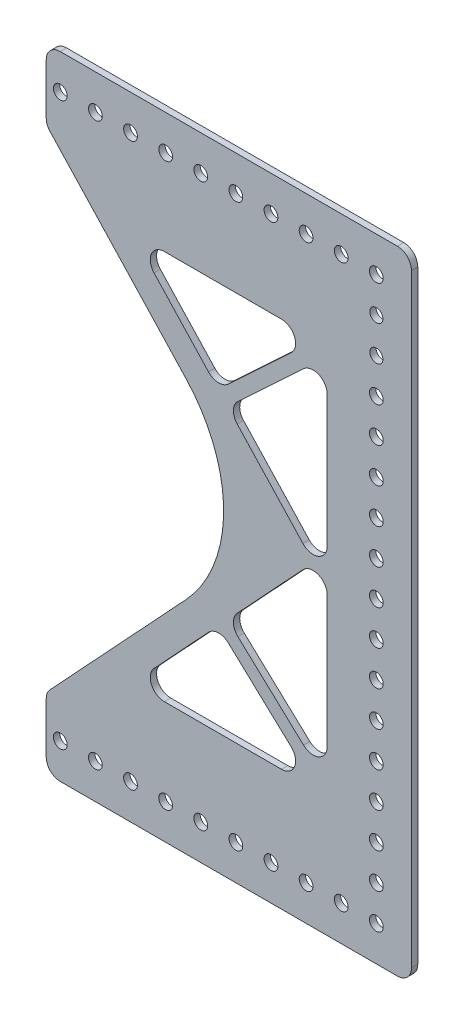
SolidWorks part; units mm, degrees
ref_plane "Front Plane" through (0, 0, 0) normal (0, 0, 1) x (1, 0, 0)
ref_plane "Top Plane" through (0, 0, 0) normal (0, 1, 0) x (1, 0, 0)
ref_plane "Right Plane" through (0, 0, 0) normal (1, 0, 0) x (0, 0, -1)
sketch "Sketch1" plane through (0, 0, 0) normal (0, 0, 1) x (1, 0, 0)
  line L0 (238.8067, 781.2872) -> (222.2967, 781.2872)
  line L4 (176.5767, 781.2872) -> (116.8867, 781.2872)
  line L5 (113.1687, 754.4243) -> (162.3479, 701.6037)
  line L6 (243.8867, 776.2072) -> (243.8867, 666.9872)
  line L7 (111.8067, 757.8859) -> (111.8067, 776.2072)
  line L8 (150.787, 728.9305) -> (170.4738, 707.786)
  line L9 (213.4067, 674.5852) -> (213.4067, 722.2064)
  line L10 (196.902, 737.4722) -> (154.5049, 737.4722)
  line L11 (243.8867, 557.7672) -> (243.8867, 666.9872)
  line L12 (238.8067, 552.6872) -> (222.2967, 552.6872)
  line L16 (113.1687, 579.55) -> (162.3479, 632.3706)
  line L17 (176.5767, 552.6872) -> (116.8867, 552.6872)
  line L18 (111.8067, 576.0884) -> (111.8067, 557.7672)
  line L19 (200.3636, 728.6742) -> (177.6534, 707.5296)
  line L20 (180.8588, 637.3423) -> (204.6087, 662.8508)
  line L21 (204.8651, 725.9243) -> (181.1151, 703.8117)
  line L22 (180.8588, 696.632) -> (204.6087, 671.1235)
  line L23 (213.4067, 659.3892) -> (213.4067, 611.768)
  line L24 (204.8651, 608.05) -> (181.1151, 630.1627)
  line L25 (200.3636, 605.3001) -> (177.6534, 626.4447)
  line L26 (150.787, 605.0438) -> (170.4738, 626.1884)
  line L27 (196.902, 596.5022) -> (154.5049, 596.5022)
  line L28 (222.2967, 552.6872) -> (176.5767, 552.6872)
  line L29 (222.2967, 781.2872) -> (176.5767, 781.2872)
  arc A0 (238.8067, 781.2872) -> (243.8867, 776.2072) centre (238.8067, 776.2072) cw
  arc A5 (116.8867, 781.2872) -> (111.8067, 776.2072) centre (116.8867, 776.2072) ccw
  circle A6 centre (142.2867, 768.5872) radius 2.4892
  circle A7 centre (154.9867, 768.5872) radius 2.4892
  circle A8 centre (167.6867, 768.5872) radius 2.4892
  circle A9 centre (231.1867, 743.1872) radius 2.3719
  circle A10 centre (231.1867, 730.4872) radius 2.4892
  circle A11 centre (231.1867, 717.7872) radius 2.4892
  circle A12 centre (231.1867, 705.0872) radius 2.4892
  circle A13 centre (231.1867, 692.3872) radius 2.4892
  arc A14 (113.1687, 754.4243) -> (111.8067, 757.8859) centre (116.8867, 757.8859) cw
  arc A15 (204.6087, 671.1235) -> (213.4067, 674.5852) centre (208.3267, 674.5852) ccw
  arc A16 (150.787, 728.9305) -> (154.5049, 737.4722) centre (154.5049, 732.3922) cw
  arc A17 (238.8067, 552.6872) -> (243.8867, 557.7672) centre (238.8067, 557.7672) ccw
  circle A22 centre (167.6867, 565.3872) radius 2.4892
  circle A23 centre (154.9867, 565.3872) radius 2.4892
  circle A24 centre (142.2867, 565.3872) radius 2.4892
  arc A25 (113.1687, 579.55) -> (111.8067, 576.0884) centre (116.8867, 576.0884) ccw
  arc A26 (116.8867, 552.6872) -> (111.8067, 557.7672) centre (116.8867, 557.7672) cw
  circle A27 centre (231.1867, 616.1872) radius 2.4892
  circle A28 centre (231.1867, 603.4872) radius 2.4892
  circle A29 centre (231.1867, 590.7872) radius 2.4892
  circle A30 centre (231.1867, 565.3872) radius 2.4892
  circle A31 centre (231.1867, 768.5872) radius 2.4892
  arc A32 (162.3479, 701.6037) -> (162.3479, 632.3706) centre (125.1681, 666.9872) cw
  circle A33 centre (231.1867, 654.2872) radius 2.4892
  circle A34 centre (231.1867, 641.5872) radius 2.4892
  circle A35 centre (231.1867, 628.8872) radius 2.4892
  circle A36 centre (116.8867, 768.5872) radius 2.4892
  circle A37 centre (129.5867, 768.5872) radius 2.4892
  circle A38 centre (129.5867, 565.3872) radius 2.4892
  circle A39 centre (116.8867, 565.3872) radius 2.4892
  arc A40 (181.1151, 703.8117) -> (180.8588, 696.632) centre (184.5767, 700.0937) ccw
  arc A41 (204.8651, 725.9243) -> (213.4067, 722.2064) centre (208.3267, 722.2064) cw
  arc A42 (200.3636, 728.6742) -> (196.902, 737.4722) centre (196.902, 732.3922) ccw
  arc A43 (177.6534, 707.5296) -> (170.4738, 707.786) centre (174.1918, 711.2476) cw
  arc A44 (204.6087, 662.8508) -> (213.4067, 659.3892) centre (208.3267, 659.3892) cw
  arc A45 (181.1151, 630.1627) -> (180.8588, 637.3423) centre (184.5767, 633.8806) cw
  arc A46 (204.8651, 608.05) -> (213.4067, 611.768) centre (208.3267, 611.768) ccw
  arc A47 (200.3636, 605.3001) -> (196.902, 596.5022) centre (196.902, 601.5822) cw
  arc A48 (177.6534, 626.4447) -> (170.4738, 626.1884) centre (174.1918, 622.7267) ccw
  arc A49 (150.787, 605.0438) -> (154.5049, 596.5022) centre (154.5049, 601.5822) ccw
  circle A50 centre (231.1867, 679.6872) radius 2.4892
  circle A51 centre (231.1867, 666.9872) radius 2.4892
  circle A52 centre (231.1867, 755.8872) radius 2.3719
  circle A53 centre (231.1867, 578.0872) radius 2.4892
  circle A54 centre (180.3867, 565.3872) radius 2.4892
  circle A55 centre (193.0867, 565.3872) radius 2.4892
  circle A56 centre (205.7867, 565.3872) radius 2.4892
  circle A57 centre (218.4867, 565.3872) radius 2.4892
  circle A58 centre (180.3867, 768.5872) radius 2.4892
  circle A59 centre (193.0867, 768.5872) radius 2.4892
  circle A60 centre (205.7867, 768.5872) radius 2.4892
  circle A61 centre (218.4867, 768.5872) radius 2.4892
  point P14 (243.8867, 666.9872)
  point P17 (218.4867, 666.9872)
  dimension "D1" = 5
  dimension "D2" = 5
extrude "Boss-Extrude1" add sketch "Sketch1" along normal blind 2.286
